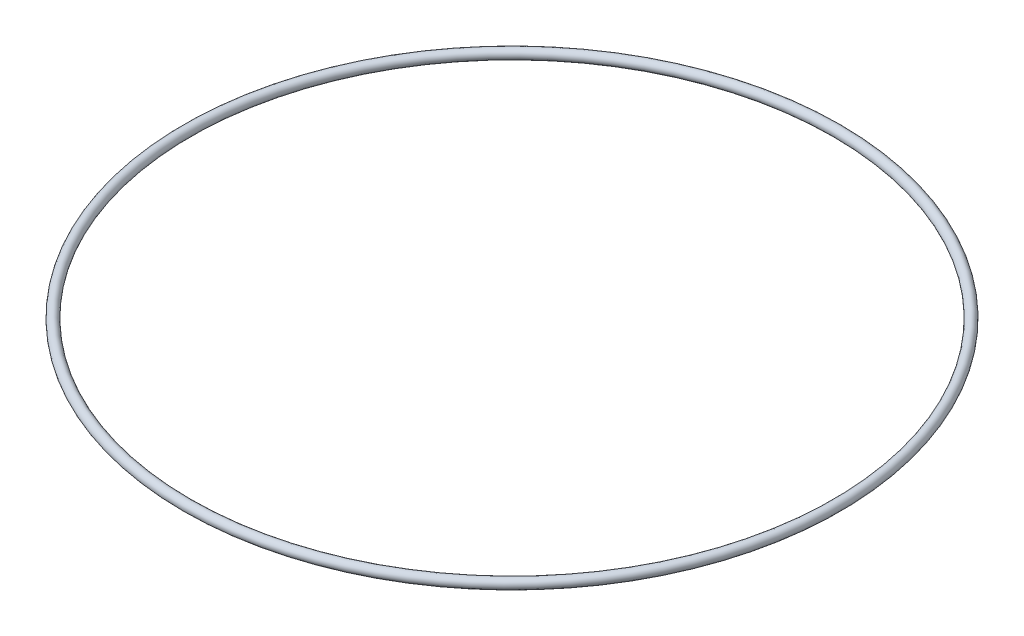
SolidWorks part; units mm, degrees
material "Rubber"
ref_plane "Front Plane" through (0, 0, 0) normal (0, 0, 1) x (1, 0, 0)
ref_plane "Top Plane" through (0, 0, 0) normal (0, 1, 0) x (1, 0, 0)
ref_plane "Right Plane" through (0, 0, 0) normal (1, 0, 0) x (0, 0, -1)
sketch "Sketch1" plane through (0, 0, 0) normal (0, 0, 1) x (1, 0, 0)
  line L0 (0, 0) -> (0, 11.8797) construction
  circle A0 centre (-66, 0) radius 1
  dimension "D1" = 2
  dimension "D2" = 65
revolve "Revolve1" add sketch "Sketch1" angle 360 about L0
